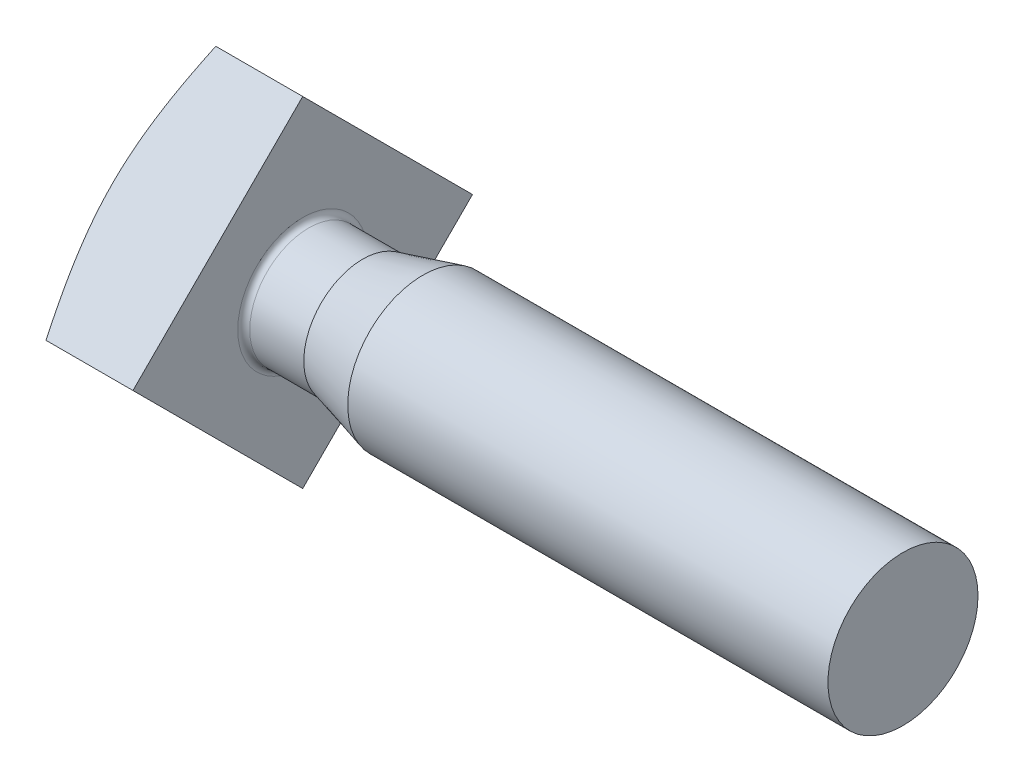
SolidWorks part; units mm, degrees
ref_plane "Front" through (0, 0, 0) normal (0, 0, 1) x (1, 0, 0)
ref_plane "Top" through (0, 0, 0) normal (0, 1, 0) x (1, 0, 0)
ref_plane "Right" through (0, 0, 0) normal (1, 0, 0) x (0, 0, -1)
sketch "Sketch2" plane through (0, 0, 0) normal (1, 0, 0) x (0, 0, -1)
  line L1 (5.6569, 0) -> (0, 5.6569)
  line L2 (0, 5.6569) -> (-5.6569, 0)
  line L3 (-5.6569, 0) -> (0, -5.6569)
  line L4 (0, -5.6569) -> (5.6569, 0)
  circle A0 centre (0, 0) radius 4 construction
extrude "BaseHead" add sketch "Sketch2" along normal blind 3.5
sketch "Sketch3" plane through (3.5, 0, 0) normal (1, 0, 0) x (0, 0, -1)
  circle A0 centre (0, 0) radius 2.5
extrude "BaseBody" add sketch "Sketch3" along normal blind 20
cosmetic thread "ThreadCosmetic1" [suppressed] parameters "b"=16, "D2"=3.75
sketch "Sketch4" plane through (0, 0, 0) normal (0, 0, 1) x (1, 0, 0)
  line L0 (0, 5.6569) -> (0.603, 5.6569)
  line L1 (0, -4) -> (0, 4) construction
  line L2 (0.603, 5.6569) -> (0, 4)
  line L4 (0, 4) -> (0, 5.6569)
  line L5 (-0.7798, 0) -> (6.4752, 0) construction
  line L7 (3.5, 5.6569) -> (0, 5.6569) construction
  dimension "D1" = 20
  dimension "D2" = 8
revolve "HeadChamfer" cut sketch "Sketch4" angle 360 about L5
sketch "Sketch5" plane through (0, 0, 0) normal (-1, 0, 0) x (0, 0, 1)
  circle A0 centre (0, 0) radius 3.6
  dimension "D1" = 7.2
extrude "Cut-Extrude1" cut sketch "Sketch5" against normal blind 0.7
sketch "Sketch6" plane through (0, 0, 0) normal (0, 0, 1) x (1, 0, 0)
  line L0 (3.5, 1.9641) -> (5.5, 1.9641)
  line L1 (5.5, 1.9641) -> (7.5, 2.5)
  line L2 (23.5, 2.5) -> (3.5, 2.5) construction
  line L3 (7.5, 2.5) -> (3.5, 2.5)
  line L4 (3.5, 2.5) -> (3.5, 1.9641)
  line L5 (3.5, -2.5) -> (3.5, 2.5) construction
  line L6 (3.5, 5.6569) -> (3.5, 0) construction
  dimension "D2" = 4
  dimension "D3" = 15
revolve "Cut-Revolve1" cut sketch "Sketch6" angle 360 about axis through (23.5, 0, 0) along (-1, 0, 0)
fillet "HeadFillet1" radius 0.2 1 edges at (3.5, 0, -1.9641)
sketch "Sketch7" plane through (0, 0, 0) normal (0, 0, 1) x (1, 0, 0)
  line L0 (23.1875, 3.125) -> (23.8125, 3.125)
  line L1 (23.8125, 3.125) -> (23.8125, 2.5)
  line L2 (23.8125, 2.5) -> (23.5, 1.9587)
  line L3 (23.5, 1.9587) -> (23.1875, 2.5)
  line L4 (23.1875, 2.5) -> (23.1875, 3.125)
  line L5 (23.5, -2.5) -> (23.5, 2.5) construction
  line L6 (23.5, 2.5) -> (7.5, 2.5) construction
  dimension "D1" = 0.625
revolve "Cut-Revolve10" [suppressed] cut sketch "Sketch7" angle 360
pattern_linear "LPattern10" [suppressed] count 21 of bodies 106
equation "\"D2@Sketch4\" = \"s@Sketch2\""
equation "\"D1@Sketch5\" = \"s@Sketch2\" * 0.9"
equation "\"D1@Cut-Extrude1\" = 0.2 * \"k@BaseHead\""
equation "\"D2@Sketch6\" = \"l@BaseBody\" - \"b@ThreadCosmetic1\""
equation "\"D1@Sketch7\" =  ( \"d@Sketch3\" - \"D2@ThreadCosmetic1\" )  / 2"
equation "\"pitch@LPattern10\" = 1.2 * \"D1@Sketch7\""
equation " \"D1@LPattern10\" = \"b@ThreadCosmetic1\" / \"pitch@LPattern10\""
